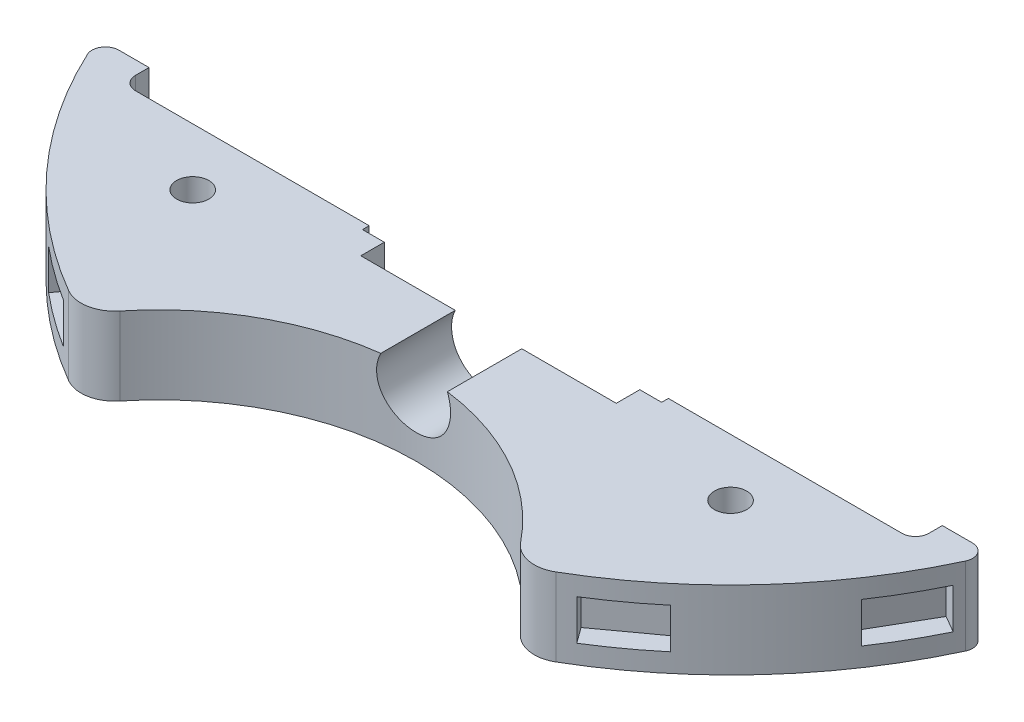
SolidWorks part; units mm, degrees
material "ABS"
ref_plane "Front Plane" through (0, 0, 0) normal (0, 0, 1) x (1, 0, 0)
ref_plane "Top Plane" through (0, 0, 0) normal (0, 1, 0) x (1, 0, 0)
ref_plane "Right Plane" through (0, 0, 0) normal (1, 0, 0) x (0, 0, -1)
sketch "Sketch1" plane through (0, 0, 0) normal (0, 1, 0) x (1, 0, 0)
  line L0 (0, -85) -> (-32.2211, -64.3879) construction
  line L1 (0, -85) -> (0, 0) construction
  arc A0 (36.2245, -62.2237) -> (-36.2245, -62.2237) centre (0, 0) ccw
  arc A1 (29.8119, -61.0352) -> (-29.8119, -61.0352) centre (0, -85) ccw
  arc A2 (36.2245, -62.2237) -> (29.8119, -61.0352) centre (33.7089, -57.9026) cw
  arc A3 (-29.8119, -61.0352) -> (-36.2245, -62.2237) centre (-33.7089, -57.9026) cw
  dimension "D1" = 144
  dimension "D2" = 76.5
  dimension "D4" = 5
  dimension "D3" = 85
extrude "Boss-Extrude1" add sketch "Sketch1" along normal mid plane 11.6
sketch "solenoid placement" plane through (0, 5.8, 0) normal (0, 1, 0) x (1, 0, 0)
  line L0 (0, 0) -> (0, -36) construction
  line L5 (-19, -36) -> (19, -36)
  line L7 (19, -36) -> (19, 28)
  line L9 (19, 28) -> (-19, 28)
  line L11 (-19, 28) -> (-19, -36)
  circle A1 centre (0, 0) radius 72 construction
  arc A2 (36.2245, -62.2237) -> (-36.2245, -62.2237) centre (0, 0) ccw construction
  point P7 (0, 28)
  dimension "D1" = 38
  dimension "D2" = 64
  dimension "D3" = 36
extrude "Cut-Extrude1" cut sketch "solenoid placement" against normal through all
sketch "Sketch6" plane through (0, 5.8, 0) normal (0, 1, 0) x (1, 0, 0)
  line L0 (0, 0) -> (0, -46.75) construction
  arc A0 (29.8119, -61.0352) -> (-29.8119, -61.0352) centre (0, -85) ccw construction
  circle A1 centre (40, -40) radius 2.4
  circle A4 centre (-40, -40) radius 2.4
  dimension "D1" = 4.8
  dimension "D2" = 40
  dimension "D3" = 40
extrude "Cut-Extrude6" cut sketch "Sketch6" against normal through all
sketch "Sketch3" plane through (0, 5.8, 0) normal (0, 1, 0) x (1, 0, 0)
  line L0 (-72, -27.5) -> (-59, -27.5)
  line L1 (-59, -31.5) -> (59, -31.5)
  line L2 (-72, -27.5) -> (-72, 31.5)
  line L3 (-59, -27.5) -> (-59, -31.5)
  line L4 (72, -27.5) -> (72, 31.5)
  line L5 (-72, 31.5) -> (72, 31.5) construction
  line L6 (0, 31.5) -> (0, -31.5) construction
  line L7 (59, -27.5) -> (59, -31.5)
  line L8 (-72, 31.5) -> (-72, 72)
  line L9 (72, -27.5) -> (59, -27.5)
  line L10 (-72, 72) -> (72, 72)
  line L11 (72, 31.5) -> (72, 72)
  arc A0 (36.2245, -62.2237) -> (-36.2245, -62.2237) centre (0, 0) ccw construction
  arc A1 (36.2245, -62.2237) -> (-36.2245, -62.2237) centre (0, 0) ccw construction
  point P0 (0, 0)
  dimension "D2" = 4
  dimension "D1" = 63
  dimension "D3" = 13
extrude "Cut-Extrude3" cut sketch "Sketch3" against normal through all
fillet "Fillet1" radius 2 4 edges at (66.5413, 0, 27.5) (59, 0, 31.5) (-66.5413, 0, 27.5) (-59, 0, 31.5)
sketch "Sketch8" plane through (0, 0, 0) normal (0, 1, 0) x (1, 0, 0)
  line L0 (0, 0) -> (62.3538, -36) construction
  line L1 (0, 0) -> (42.3205, -58.2492) construction
  line L2 (0, 0) -> (14.9696, -70.4266) construction
  line L3 (0, 0) -> (-14.9696, -70.4266) construction
  line L4 (-42.3205, -58.2492) -> (0, 0) construction
  line L5 (0, 0) -> (-62.3538, -36) construction
  line L6 (0, 0) -> (0, -72) construction
  arc A0 (-62.3538, -36) -> (-42.3205, -58.2492) centre (0, 0) ccw construction
  arc A1 (62.3538, -36) -> (42.3205, -58.2492) centre (0, 0) cw construction
  arc A2 (14.9696, -70.4266) -> (42.3205, -58.2492) centre (0, 0) ccw construction
  arc A3 (14.9696, -70.4266) -> (-14.9696, -70.4266) centre (0, 0) cw construction
  arc A4 (-14.9696, -70.4266) -> (-42.3205, -58.2492) centre (0, 0) cw construction
  arc A5 (36.2245, -62.2237) -> (65.294, -30.3429) centre (0, 0) ccw construction
  dimension "D1" = 120
sketch "Sketch9" plane through (0, 0, 0) normal (0, 1, 0) x (1, 0, 0)
  line L0 (0, 0) -> (-59.7033, -40.2432) construction
  line L1 (0, 0) -> (-64.7033, -31.583) construction
  line L2 (-64.7033, -31.583) -> (-59.7033, -40.2432) construction
  line L3 (-64.7033, -31.583) -> (-62.1918, -30.133)
  line L4 (-62.1918, -30.133) -> (-57.1918, -38.7932)
  line L5 (-57.1918, -38.7932) -> (-59.7033, -40.2432)
  line L6 (-46.2635, -55.1697) -> (-44.5589, -52.8235)
  line L7 (-44.5589, -52.8235) -> (-36.4687, -58.7014)
  line L8 (-36.4687, -58.7014) -> (-38.1733, -61.0475)
  line L9 (0, 0) -> (-38.1733, -61.0475) construction
  line L10 (0, 0) -> (-46.2635, -55.1697) construction
  line L11 (-46.2635, -55.1697) -> (-38.1733, -61.0475) construction
  line L12 (-19.8242, -69.217) -> (-19.2213, -66.3804) [skipped]
  line L13 (-19.2213, -66.3804) -> (-9.4398, -68.4595) [skipped]
  line L14 (-9.4398, -68.4595) -> (-10.0428, -71.2962) [skipped]
  line L15 (0, 0) -> (-10.0428, -71.2962) construction
  line L16 (0, 0) -> (-19.8242, -69.217) construction
  line L17 (-19.8242, -69.217) -> (-10.0428, -71.2962) construction
  line L18 (10.0428, -71.2962) -> (9.4398, -68.4595) [skipped]
  line L19 (9.4398, -68.4595) -> (19.2213, -66.3804) [skipped]
  line L20 (19.2213, -66.3804) -> (19.8242, -69.217) [skipped]
  line L21 (0, 0) -> (19.8242, -69.217) construction
  line L22 (0, 0) -> (10.0428, -71.2962) construction
  line L23 (10.0428, -71.2962) -> (19.8242, -69.217) construction
  line L24 (38.1733, -61.0475) -> (36.4687, -58.7014)
  line L25 (36.4687, -58.7014) -> (44.5589, -52.8235)
  line L26 (44.5589, -52.8235) -> (46.2635, -55.1697)
  line L27 (0, 0) -> (46.2635, -55.1697) construction
  line L28 (0, 0) -> (38.1733, -61.0475) construction
  line L29 (38.1733, -61.0475) -> (46.2635, -55.1697) construction
  line L30 (59.7033, -40.2432) -> (57.1918, -38.7932)
  line L31 (57.1918, -38.7932) -> (62.1918, -30.133)
  line L32 (62.1918, -30.133) -> (64.7033, -31.583)
  line L33 (0, 0) -> (64.7033, -31.583) construction
  line L34 (0, 0) -> (59.7033, -40.2432) construction
  line L35 (59.7033, -40.2432) -> (64.7033, -31.583) construction
  arc A0 (-59.7033, -40.2432) -> (-64.7033, -31.583) centre (0, 0) cw
  arc A1 (-62.3538, -36) -> (-42.3205, -58.2492) centre (0, 0) ccw construction
  arc A2 (-38.1733, -61.0475) -> (-46.2635, -55.1697) centre (0, 0) cw
  arc A3 (-10.0428, -71.2962) -> (-19.8242, -69.217) centre (0, 0) cw [skipped]
  arc A4 (19.8242, -69.217) -> (10.0428, -71.2962) centre (0, 0) cw [skipped]
  arc A5 (46.2635, -55.1697) -> (38.1733, -61.0475) centre (0, 0) cw
  arc A6 (64.7033, -31.583) -> (59.7033, -40.2432) centre (0, 0) cw
  point P8 (-62.3538, -36)
  point P12 (62.3538, -36)
  point P34 (0, 0)
  dimension "D1" = 10
  dimension "D2" = 2.9
  dimension "D3" = 6
extrude "Cut-Extrude7" cut sketch "Sketch9" against normal mid plane 6
sketch "Sketch11" plane through (0, 0, 36) normal (0, 0, -1) x (-1, 0, 0)
  line L0 (0, -5.8) -> (0, 3.4) construction
  line L1 (19, -5.8) -> (-19, -5.8) construction
  circle A0 centre (0, 3.4) radius 5.5
  dimension "D2" = 11
  dimension "D1" = 9.2
extrude "Cut-Extrude8" cut sketch "Sketch11" against normal through all
sketch "Sketch12" plane through (0, 5.8, 0) normal (0, 1, 0) x (1, 0, 0)
  line L1 (-22.25, 32.5) -> (22.25, 32.5)
  line L2 (-22.25, 32.5) -> (-22.25, -32.5)
  line L3 (-22.25, -32.5) -> (22.25, -32.5)
  line L4 (22.25, 32.5) -> (22.25, -32.5)
  line L5 (-22.25, 32.5) -> (22.25, -32.5) construction
  line L6 (-22.25, -32.5) -> (22.25, 32.5) construction
  point P0 (0, 0)
  dimension "D1" = 44.5
  dimension "D2" = 65
extrude "Cut-Extrude9" cut sketch "Sketch12" against normal through all
equation "\"smallPulleyTeeth\"= 15"
equation "\"largePulleyTeeth\"= 30"
equation "\"eighthThick\"= 2.9mm"
equation "\"sixteenthThick\" = 1.7mm"
equation "\"quarterThick\"=6.0mm"
equation "\"OD\" = 145mm"
equation "\"puckAngle\" = 60.5deg"
equation "\"puckDiam\" = 76.5mm"
equation "\"D2@Sketch1\"=\"puckDiam\""
equation "\"D1@Boss-Extrude1\"=\"eighthThick\"*4"
equation "\"axlePress\" = 5.9mm"
equation "\"press\" = 0.2mm"
equation "\"wheelClear\" = 0.3mm"
equation "\"10-32clear\" = 4.8mm"
equation "\"6-32clear\" = 3.3mm"
equation "\"8-32clear\" = 4.0mm"
equation "\"wheelHeight\" = 22mm"
equation "\"wheelWell\" = 65mm"
equation "\"puckDist\" = 85mm"
equation "\"scoopFillet\" = 5mm"
equation "\"4-40clear\" = 3.0mm"
equation "\"D3@Sketch1\"=\"puckDist\""
equation "\"D4@Sketch1\"=\"scoopFillet\""
equation "\"D1@Sketch6\"=\"10-32clear\""
equation "\"D2@Sketch9\"=\"eighthThick\""
equation "\"D2@Sketch12\"=\"wheelWell\""
